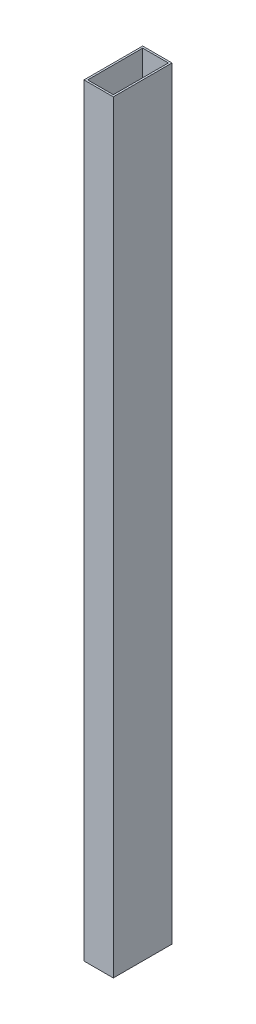
SolidWorks part; units mm, degrees
material "6061-T6 (SS)"
ref_plane "Front" through (0, 0, 0) normal (0, 0, 1) x (1, 0, 0)
ref_plane "Top" through (0, 0, 0) normal (0, 1, 0) x (1, 0, 0)
ref_plane "Right" through (0, 0, 0) normal (1, 0, 0) x (0, 0, -1)
sketch "Sketch1" plane through (0, 0, 0) normal (0, 1, 0) x (1, 0, 0)
  line L1 (12.7, 25.4) -> (-12.7, 25.4)
  line L2 (12.7, 25.4) -> (12.7, -25.4)
  line L3 (12.7, -25.4) -> (-12.7, -25.4)
  line L4 (-12.7, 25.4) -> (-12.7, -25.4)
  line L5 (12.7, 25.4) -> (-12.7, -25.4) construction
  line L6 (12.7, -25.4) -> (-12.7, 25.4) construction
  point P0 (0, 0)
  dimension "D1" = 25.4
  dimension "D2" = 50.8
extrude "Extrude-Thin1" add sketch "Sketch1" along normal up to surface (660.4 mm away) thin thin type one direction reverse wall 1.5875
